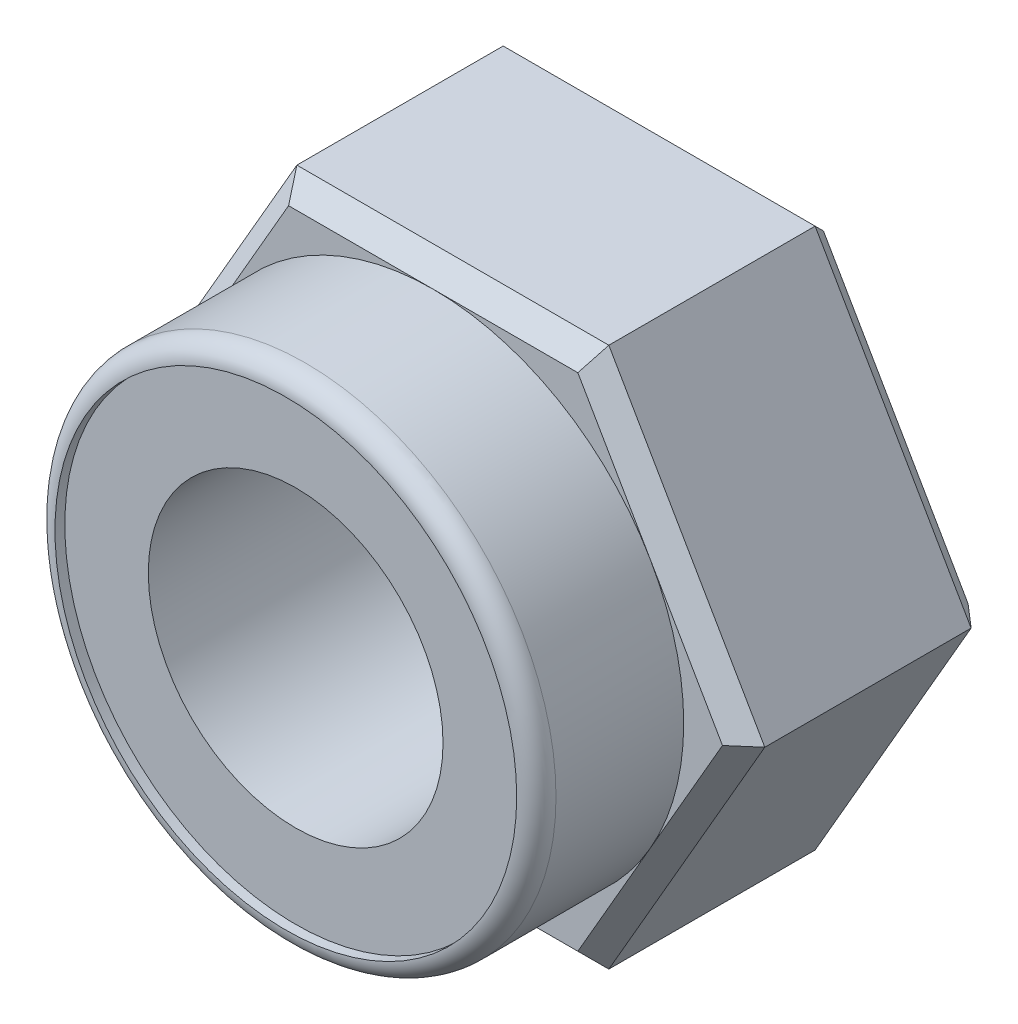
SolidWorks part; units mm, degrees
ref_plane "Front Plane" through (0, 0, 0) normal (0, 0, 1) x (1, 0, 0)
ref_plane "Top Plane" through (0, 0, 0) normal (0, 1, 0) x (1, 0, 0)
ref_plane "Right Plane" through (0, 0, 0) normal (1, 0, 0) x (0, 0, -1)
sketch "Sketch1" plane through (0, 0, 0) normal (0, 0, 1) x (1, 0, 0)
  line L1 (-1.5877, -2.75) -> (1.5877, -2.75)
  line L2 (1.5877, -2.75) -> (3.1754, 0)
  line L3 (3.1754, 0) -> (1.5877, 2.75)
  line L4 (1.5877, 2.75) -> (-1.5877, 2.75)
  line L5 (-1.5877, 2.75) -> (-3.1754, 0)
  line L6 (-3.1754, 0) -> (-1.5877, -2.75)
  circle A0 centre (0, 0) radius 2.75 construction
  circle A1 centre (0, 0) radius 1.5
  dimension "D2" = 3
  dimension "D1" = 5.5
extrude "Shape" add sketch "Sketch1" along normal blind 2.5
chamfer "Chamfer" distance 0.2 angle 45 12 edges at (2.3816, -1.375, 0) (0, -2.75, 0) (-2.3816, -1.375, 0) (-2.3816, 1.375, 0) (0, 2.75, 0) (2.3816, 1.375, 0) (2.3816, 1.375, 2.5) (2.3816, -1.375, 2.5) (0, -2.75, 2.5) (-2.3816, -1.375, 2.5) (-2.3816, 1.375, 2.5) (0, 2.75, 2.5)
ref_axis "Center Axis" through (0, 0, 2.5) along (0, 0, -1)
sketch "Sketch2" plane through (0, 0, 2.5) normal (0, 0, 1) x (1, 0, 0)
  line L0 (2.9445, 0) -> (1.4722, 2.55) construction
  circle A0 centre (0, 0) radius 1.5 construction
  circle A1 centre (0, 0) radius 1.5
  circle A2 centre (0, 0) radius 2.55
extrude "Boss-Extrude2" add sketch "Sketch2" along normal offset from surface (1.5 mm away) 4 up to face at (0, 0, 0)
fillet "Fillet1" radius 0.2 1 edges at (2.55, 0, 4)
sketch "Sketch3" plane through (0, 0, 4) normal (0, 0, 1) x (1, 0, 0)
  circle A0 centre (0, 0) radius 2.35 construction
  circle A1 centre (0, 0) radius 2.35
  circle A2 centre (0, 0) radius 1.5 construction
  circle A3 centre (0, 0) radius 1.5
extrude "Cut-Extrude1" cut sketch "Sketch3" against normal blind 0.1
